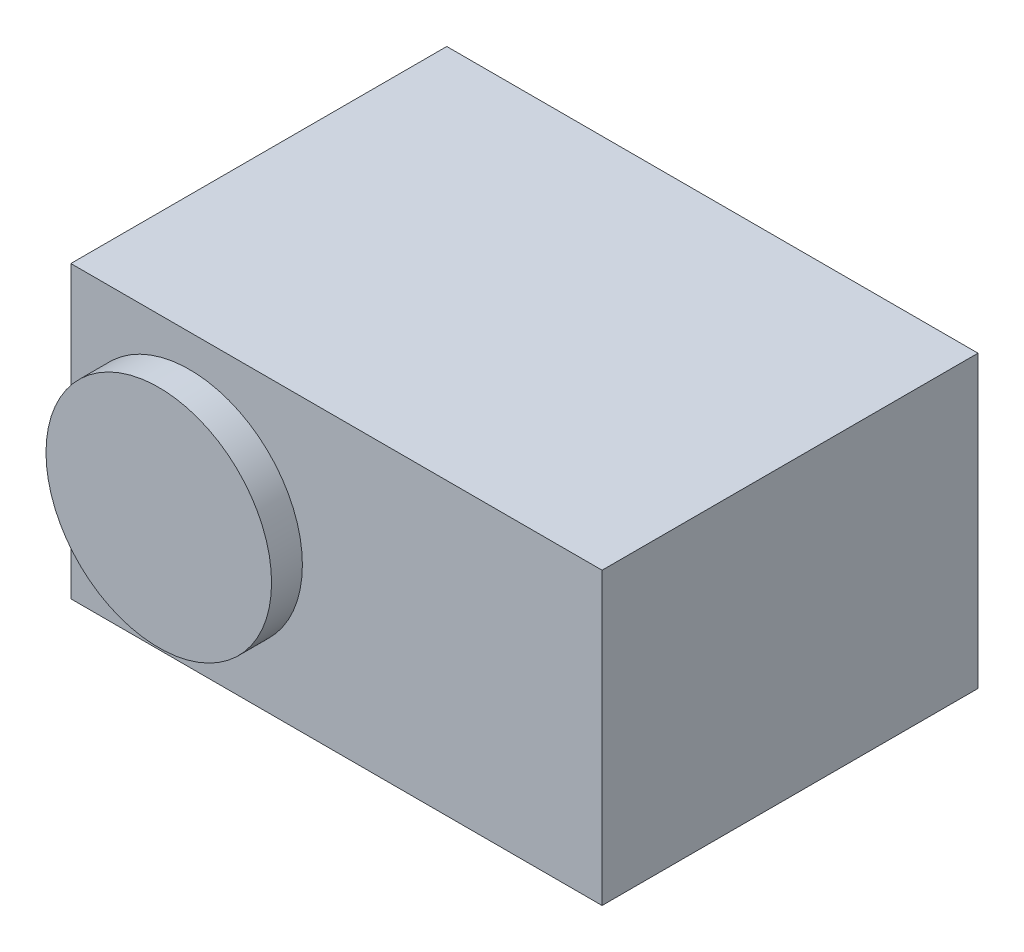
SolidWorks part; units mm, degrees
ref_plane "Front Plane" through (0, 0, 0) normal (0, 0, 1) x (1, 0, 0)
ref_plane "Top Plane" through (0, 0, 0) normal (0, 1, 0) x (1, 0, 0)
ref_plane "Right Plane" through (0, 0, 0) normal (1, 0, 0) x (0, 0, -1)
ref_plane "PZ_m16_000" through (0, 0, -16) normal (0, 0, 1) x (1, 0, 0)
sketch "S_box1" plane through (0, 0, -16) normal (0, 0, 1) x (1, 0, 0)
  line L0 (-10.11, -12.36) -> (35.11, -12.36)
  line L1 (35.11, -12.36) -> (35.11, 12.36)
  line L2 (35.11, 12.36) -> (-10.11, 12.36)
  line L3 (-10.11, 12.36) -> (-10.11, -12.36)
  dimension "P1" = 10.11
  dimension "P2" = 12.36
  dimension "P3" = 35.11
  dimension "P4" = 12.36
  dimension "P5" = 35.11
  dimension "P6" = 12.36
  dimension "P7" = 10.11
  dimension "P8" = 12.36
extrude "Boss_1" add sketch "S_box1" along normal blind 32
ref_plane "PZ_p15_500" through (0, 0, 15.5) normal (0, 0, 1) x (1, 0, 0)
sketch "S_cyl2" plane through (0, 0, 15.5) normal (0, 0, 1) x (1, 0, 0)
  circle A0 centre (0, 0) radius 9.6
  dimension "D1_S_cyl2" = 19.2
extrude "Boss_2" add sketch "S_cyl2" along normal blind 3.125
ref_plane "PZ_m18_625" through (0, 0, -18.625) normal (0, 0, 1) x (1, 0, 0)
sketch "S_cyl3" plane through (0, 0, -18.625) normal (0, 0, 1) x (1, 0, 0)
  circle A0 centre (0, 0) radius 9.6
  dimension "D1_S_cyl3" = 19.2
extrude "Boss_3" add sketch "S_cyl3" along normal blind 3.125
ref_plane "PZ_p17_625" through (0, 0, 17.625) normal (0, 0, 1) x (1, 0, 0)
sketch "S_hole4" plane through (0, 0, 17.625) normal (0, 0, 1) x (1, 0, 0)
  circle A0 centre (4.9497, 4.9497) radius 1.35
  dimension "D1_S_hole4" = 2.7
  dimension "P2" = 4.9497
  dimension "P3" = 4.9497
extrude "Hole_4" cut sketch "S_hole4" against normal blind 1.1
sketch "S_hole5" plane through (0, 0, 17.625) normal (0, 0, 1) x (1, 0, 0)
  circle A0 centre (-4.9497, 4.9497) radius 1.35
  dimension "D1_S_hole5" = 2.7
  dimension "P2" = 4.9497
  dimension "P3" = 4.9497
extrude "Hole_5" cut sketch "S_hole5" against normal blind 1.1
sketch "S_hole6" plane through (0, 0, 17.625) normal (0, 0, 1) x (1, 0, 0)
  circle A0 centre (-4.9497, -4.9497) radius 1.35
  dimension "D1_S_hole6" = 2.7
  dimension "P2" = 4.9497
  dimension "P3" = 4.9497
extrude "Hole_6" cut sketch "S_hole6" against normal blind 1.1
sketch "S_hole7" plane through (0, 0, 17.625) normal (0, 0, 1) x (1, 0, 0)
  circle A0 centre (4.9497, -4.9497) radius 1.35
  dimension "D1_S_hole7" = 2.7
  dimension "P2" = 4.9497
  dimension "P3" = 4.9497
extrude "Hole_7" cut sketch "S_hole7" against normal blind 1.1
equation "\"plate_t\" = 3"
equation "\"clearance\" = 0.4"
